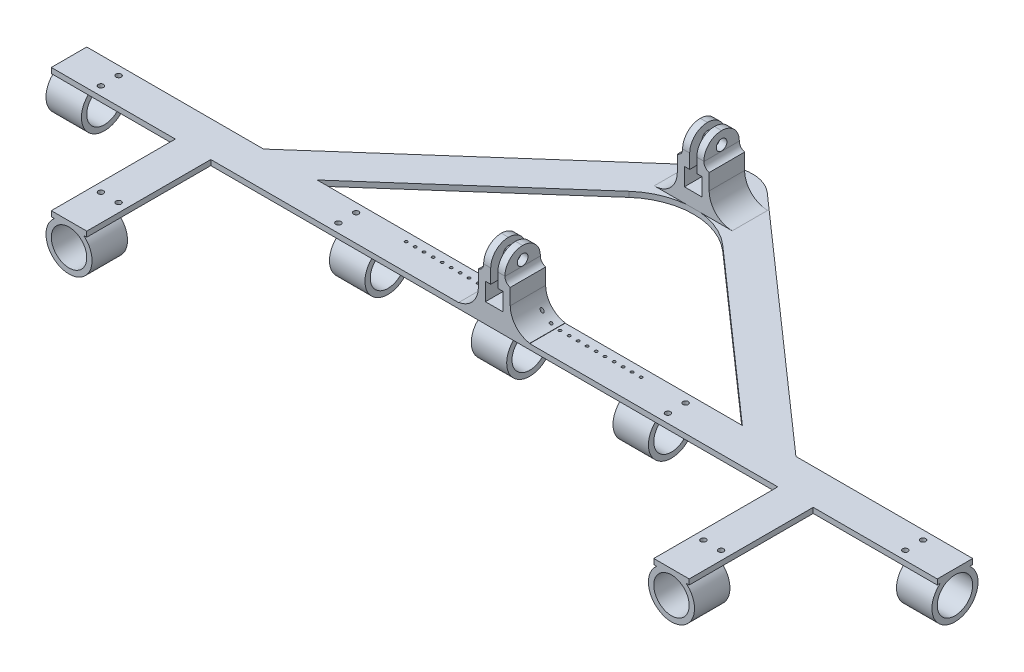
SolidWorks part; units mm, degrees
ref_plane "前视基准面" through (0, 0, 0) normal (0, 0, 1) x (1, 0, 0)
ref_plane "上视基准面" through (0, 0, 0) normal (0, 1, 0) x (1, 0, 0)
ref_plane "右视基准面" through (0, 0, 0) normal (1, 0, 0) x (0, 0, -1)
sketch "草图1" plane through (0, 0, 0) normal (0, 1, 0) x (1, 0, 0)
  line L1 (-125, 5) -> (125, 5)
  line L2 (-125, 5) -> (-125, -5)
  line L3 (-125, -5) -> (125, -5)
  line L4 (125, 5) -> (125, -5)
  line L5 (-125, 5) -> (125, -5) construction
  line L6 (-125, -5) -> (125, 5) construction
  point P0 (0, 0)
  dimension "D1" = 250
  dimension "D2" = 10
extrude "凸台-拉伸1" add sketch "草图1" along normal blind 1.5
sketch "草图4" plane through (0, 0, 0) normal (0, -1, 0) x (1, 0, 0)
  line L1 (-5, 7.1337) -> (5, 7.1337)
  line L2 (-5, 7.1337) -> (-5, -7.1337)
  line L3 (-5, -7.1337) -> (5, -7.1337)
  line L4 (5, 7.1337) -> (5, -7.1337)
  line L5 (-5, 7.1337) -> (5, -7.1337) construction
  line L6 (-5, -7.1337) -> (5, 7.1337) construction
  point P0 (0, 0)
  dimension "D1" = 10
  dimension "D2" = 14.2673
extrude "凸台-拉伸3" add sketch "草图4" along normal blind 11.5
sketch "草图5" plane through (5, 0, 0) normal (1, 0, 0) x (0, 0, -1)
  line L0 (0, 0) -> (0, -5)
  line L1 (5, 0) -> (-5, 0) construction
  line L2 (-5, 1.5) -> (5, 1.5) construction
  circle A0 centre (0, -5) radius 5
  circle A1 centre (0, -5) radius 6.5
  line M1 (7.1337, 0) -> (5, 0)
  line M2 (5, 0) -> (-5, 0)
  line M3 (-5, 0) -> (-7.1337, 0)
  line M4 (-7.1337, 0) -> (-7.1337, -11.5)
  line M5 (-7.1337, -11.5) -> (7.1337, -11.5)
  line M6 (7.1337, -11.5) -> (7.1337, 0)
  dimension "D1" = 10
extrude "切除-拉伸1" cut sketch "草图5" against normal through all contours A1 M2 M3 M4 M5 | A1 M5 M6 M1 M2 | A0 region at (5, -8.4355, 3.4355) region at (5, -0.1353, -4.5767) region at (5, -7.2539, 6.2408)
sketch "草图6" plane through (0, 0, 0) normal (0, -1, 0) x (1, 0, 0)
  line L0 (0, 0) -> (40, 0)
  line L1 (-125, 5) -> (125, 5) construction
  line L3 (35, 6.5) -> (45, 6.5)
  line L4 (35, 6.5) -> (35, -6.5)
  line L5 (35, -6.5) -> (45, -6.5)
  line L6 (45, 6.5) -> (45, -6.5)
  line L7 (35, 6.5) -> (45, -6.5) construction
  line L8 (35, -6.5) -> (45, 6.5) construction
  dimension "D1" = 40
  dimension "D2" = 10
  dimension "D3" = 13
extrude "凸台-拉伸4" add sketch "草图6" along normal blind 11.5 contours L3 L6 L5 L4
sketch "草图7" plane through (45, 0, 0) normal (1, 0, 0) x (0, 0, -1)
  line L0 (0, -5) -> (0, 0)
  line L1 (-5, 0) -> (5, 0) construction
  line L2 (-5, 1.5) -> (5, 1.5) construction
  circle A0 centre (0, -5) radius 5
  circle A1 centre (0, -5) radius 6.5
  line M1 (-5, 0) -> (-6.5, 0)
  line M2 (-6.5, 0) -> (-6.5, -11.5)
  line M3 (-6.5, -11.5) -> (6.5, -11.5)
  line M4 (6.5, -11.5) -> (6.5, 0)
  line M5 (6.5, 0) -> (5, 0)
  line M6 (5, 0) -> (-5, 0)
  dimension "D1" = 10
extrude "切除-拉伸2" cut sketch "草图7" against normal through all contours A1 M6 M1 M2 | A1 M2 M3 | A1 M3 M4 | A1 M4 M5 M6 | A0 region at (45, -8.4355, 3.4355) region at (45, -1.2004, -5.8248) region at (45, -1.2004, 5.8248) region at (45, -10.0481, -5.0481) region at (45, -10.0481, 5.0481)
sketch "草图8" plane through (0, 0, 0) normal (0, -1, 0) x (1, 0, 0)
  line L0 (0, 0) -> (120, 0)
  line L1 (-125, 5) -> (125, 5) construction
  line L3 (115, 6.5) -> (125, 6.5)
  line L4 (115, 6.5) -> (115, -6.5)
  line L5 (115, -6.5) -> (125, -6.5)
  line L6 (125, 6.5) -> (125, -6.5)
  line L7 (115, 6.5) -> (125, -6.5) construction
  line L8 (115, -6.5) -> (125, 6.5) construction
  dimension "D1" = 120
  dimension "D2" = 10
  dimension "D3" = 13
extrude "凸台-拉伸5" add sketch "草图8" along normal blind 11.5 contours L3 L6 L5 L4
sketch "草图9" plane through (125, 0, 0) normal (1, 0, 0) x (0, 0, -1)
  line L0 (0, -5) -> (0, 0)
  line L1 (-5, 1.5) -> (5, 1.5) construction
  line L2 (-5, 0) -> (5, 0)
  circle A0 centre (0, -5) radius 5
  circle A1 centre (0, -5) radius 6.5
  line M2 (-5, 0) -> (-6.5, 0)
  line M3 (-6.5, 0) -> (-6.5, -11.5)
  line M4 (-6.5, -11.5) -> (6.5, -11.5)
  line M5 (6.5, -11.5) -> (6.5, 0)
  line M6 (6.5, 0) -> (5, 0)
  dimension "D1" = 10
extrude "切除-拉伸3" cut sketch "草图9" against normal through all contours A1 L2 M2 M3 | A1 M3 M4 | A1 M4 M5 | A1 L2 M5 M6 | A0 region at (125, -1.2004, 5.8248) region at (125, -1.5645, -3.4355) region at (125, -1.2004, -5.8248) region at (125, -10.0481, 5.0481) region at (125, -10.0481, -5.0481)
sketch "草图13" plane through (0, 0, 0) normal (0, -1, 0) x (1, 0, 0)
  line L0 (0, 0) -> (-40, 0)
  line L1 (-125, 5) -> (125, 5) construction
  line L3 (-45, 6.5) -> (-35, 6.5)
  line L4 (-45, 6.5) -> (-45, -6.5)
  line L5 (-45, -6.5) -> (-35, -6.5)
  line L6 (-35, 6.5) -> (-35, -6.5)
  line L7 (-45, 6.5) -> (-35, -6.5) construction
  line L8 (-45, -6.5) -> (-35, 6.5) construction
  dimension "D1" = 40
  dimension "D2" = 10
  dimension "D3" = 13
extrude "凸台-拉伸6" add sketch "草图13" along normal blind 11.5 contours L3 L6 L5 L4
sketch "草图15" plane through (-45, 0, 0) normal (-1, 0, 0) x (0, 0, 1)
  line L0 (0, 0) -> (0, -5)
  line L1 (-5, 1.5) -> (5, 1.5) construction
  circle A0 centre (0, -5) radius 5
  circle A1 centre (0, -5) radius 6.5
  line M1 (6.5, 0) -> (5, 0)
  line M2 (5, 0) -> (-5, 0)
  line M3 (-5, 0) -> (-6.5, 0)
  line M4 (-6.5, 0) -> (-6.5, -11.5)
  line M5 (-6.5, -11.5) -> (6.5, -11.5)
  line M6 (6.5, -11.5) -> (6.5, 0)
  dimension "D1" = 10
extrude "切除-拉伸5" cut sketch "草图15" against normal through all contours A1 M2 M3 M4 | A1 M4 M5 | A1 M6 M1 M2 | A1 M5 M6 | A0 region at (-45, -8.4355, -3.4355) region at (-45, -1.2004, 5.8248) region at (-45, -1.2004, -5.8248) region at (-45, -10.0481, 5.0481) region at (-45, -10.0481, -5.0481)
sketch "草图16" plane through (0, 0, 0) normal (0, -1, 0) x (1, 0, 0)
  line L0 (0, 0) -> (-120, 0)
  line L1 (-125, 5) -> (125, 5) construction
  line L3 (-125, 6.5) -> (-115, 6.5)
  line L4 (-125, 6.5) -> (-125, -6.5)
  line L5 (-125, -6.5) -> (-115, -6.5)
  line L6 (-115, 6.5) -> (-115, -6.5)
  line L7 (-125, 6.5) -> (-115, -6.5) construction
  line L8 (-125, -6.5) -> (-115, 6.5) construction
  dimension "D1" = 120
  dimension "D2" = 10
  dimension "D3" = 13
extrude "凸台-拉伸7" add sketch "草图16" along normal blind 11.5 contours L3 L6 L5 L4
sketch "草图17" plane through (-125, 0, 0) normal (-1, 0, 0) x (0, 0, 1)
  line L0 (0, -5) -> (0, 0)
  line L1 (-5, 1.5) -> (5, 1.5) construction
  line L2 (-5, 0) -> (5, 0)
  circle A0 centre (0, -5) radius 5
  circle A1 centre (0, -5) radius 6.5
  line M2 (-5, 0) -> (-6.5, 0)
  line M3 (-6.5, 0) -> (-6.5, -11.5)
  line M4 (-6.5, -11.5) -> (6.5, -11.5)
  line M5 (6.5, -11.5) -> (6.5, 0)
  line M6 (6.5, 0) -> (5, 0)
  dimension "D1" = 10
extrude "切除-拉伸6" cut sketch "草图17" against normal through all contours A1 L2 M2 M3 | A1 M3 M4 | A1 M4 M5 | A1 L2 M5 M6 | A0 region at (-125, -1.2004, -5.8248) region at (-125, -1.5645, 3.4355) region at (-125, -1.2004, 5.8248) region at (-125, -10.0481, -5.0481) region at (-125, -10.0481, 5.0481)
sketch "草图18" plane through (0, 0, 0) normal (0, -1, 0) x (1, 0, 0)
  line L0 (-117.1464, 2.5) -> (-107.1464, 2.5)
  line L1 (-125, 5) -> (125, 5) construction
  line L2 (-140.924, 0) -> (135.605, 0) construction
  line L3 (0, 37.3305) -> (0, -40.1844) construction
  line L4 (-117.1464, -2.5) -> (-107.1464, -2.5)
  line L5 (117.1464, -2.5) -> (107.1464, -2.5)
  line L6 (117.1464, 2.5) -> (107.1464, 2.5)
  line L7 (-51.9294, 2.5) -> (-41.9294, 2.5)
  line L8 (-51.9294, -2.5) -> (-41.9294, -2.5)
  line L9 (51.9294, -2.5) -> (41.9294, -2.5)
  line L10 (51.9294, 2.5) -> (41.9294, 2.5)
  line L11 (-113.5, 7.6526) -> (-113.5, -7.9222)
  line L12 (-115, -6.5) -> (-115, 6.5) construction
  line L13 (-46.5, 7.6526) -> (-46.5, -7.9222)
  line L14 (-45, 6.5) -> (-45, -6.5) construction
  line L15 (46.5, 7.6526) -> (46.5, -7.9222)
  line L16 (113.5, 7.6526) -> (113.5, -7.9222)
  line L17 (-1.8696, 2.5) -> (-11.8696, 2.5)
  line L18 (-1.8696, -2.5) -> (-11.8696, -2.5)
  line L19 (-6.5, 7.6526) -> (-6.5, -7.9222)
  line L20 (-5, 6.5) -> (-5, -6.5) construction
  circle A0 centre (-113.5, 2.5) radius 0.75
  circle A1 centre (-113.5, -2.5) radius 0.75
  circle A2 centre (-46.5, 2.5) radius 0.75
  circle A3 centre (-46.5, -2.5) radius 0.75
  circle A4 centre (46.5, -2.5) radius 0.75
  circle A5 centre (46.5, 2.5) radius 0.75
  circle A6 centre (113.5, -2.5) radius 0.75
  circle A7 centre (113.5, 2.5) radius 0.75
  circle A8 centre (-6.5, 2.5) radius 0.75
  circle A9 centre (-6.5, -2.5) radius 0.75
  point P44 (-113.5, 2.5)
  point P45 (-113.5, -2.5)
  point P50 (-46.5, 2.5)
  point P51 (-46.5, -2.5)
  point P64 (-6.5, 2.5)
  point P65 (-6.5, -2.5)
  dimension "D8" = 1.5
  dimension "D9" = 1.5
  dimension "D10" = 1.5
  dimension "D1" = 2.5
  dimension "D2" = 10
  dimension "D3" = 10
  dimension "D4" = 1.5
  dimension "D5" = 1.5
  dimension "D6" = 10
  dimension "D7" = 1.5
extrude "切除-拉伸8" cut sketch "草图18" against normal through all contours L11 A0 L0 | L0 A0 L11 | L11 A0 L0 | L0 A0 L11 | A1 L4 L11 | A1 L11 L4 | A1 L4 L11 | A1 L11 L4 | L13 A2 L7 | L7 A2 L13 | L7 A2 L13 | L13 A2 L7 | A3 L8 L13 | A3 L13 L8 | A3 L13 L8 | A3 L8 L13 | L17 A8 L19 | L19 A8 L17 | L19 A8 L17 | L17 A8 L19 | A9 L18 L19 | A9 L19 L18 | A9 L18 L19 | A9 L19 L18 | A5 L10 L15 | A5 L15 L10 | A5 L10 L15 | A5 L15 L10 | L15 A4 L9 | L9 A4 L15 | L15 A4 L9 | L9 A4 L15 | A7 L6 L16 | A7 L16 L6 | A7 L6 L16 | A7 L16 L6 | L16 A6 L5 | L5 A6 L16 | L16 A6 L5 | L5 A6 L16 region at (-113.8183, 0, 2.8183) region at (-113.1817, 0, -2.1817) region at (-113.8183, 0, -2.1817) region at (-113.8183, 0, 2.1817) region at (-113.1817, 0, 2.8183) region at (-113.1817, 0, 2.1817) region at (-113.8183, 0, -2.8183) region at (-113.1817, 0, -2.8183) region at (113.8183, 0, -2.8183) region at (113.8183, 0, -2.1817) region at (113.1817, 0, 2.1817) region at (113.8183, 0, 2.1817) region at (113.1817, 0, -2.8183) region at (113.1817, 0, -2.1817) region at (113.8183, 0, 2.8183) region at (113.1817, 0, 2.8183) region at (-46.8183, 0, 2.8183) region at (-46.1817, 0, -2.1817) region at (-46.8183, 0, -2.1817) region at (-46.8183, 0, 2.1817) region at (-46.1817, 0, 2.8183) region at (-46.1817, 0, 2.1817) region at (-46.8183, 0, -2.8183) region at (-46.1817, 0, -2.8183) region at (46.8183, 0, -2.8183) region at (46.8183, 0, -2.1817) region at (46.1817, 0, 2.1817) region at (46.8183, 0, 2.1817) region at (46.1817, 0, -2.8183) region at (46.1817, 0, -2.1817) region at (46.8183, 0, 2.8183) region at (46.1817, 0, 2.8183) region at (-6.1817, 0, 2.1817) region at (-6.1817, 0, 2.8183) region at (-6.1817, 0, -2.1817) region at (-6.8183, 0, -2.1817) region at (-6.8183, 0, 2.1817) region at (-6.8183, 0, 2.8183) region at (-6.8183, 0, -2.8183) region at (-6.1817, 0, -2.8183)
sketch "草图22" plane through (0, 0, 0) normal (0, -1, 0) x (1, 0, 0)
  line L0 (0, 107.0541) -> (0, -222.8841) construction
  line L1 (0, 0) -> (-60, 0)
  line L2 (-125, 5) -> (125, 5) construction
  line L4 (125, -5) -> (-125, -5) construction
  line L5 (60, 0) -> (60, -5)
  line L6 (-60, -5) -> (0, -57.915)
  line L7 (0, -57.915) -> (60, -5)
  line L8 (-75.1186, -5) -> (0, -71.2484)
  line L9 (0, -71.2484) -> (75.1186, -5)
  line L10 (-60, -5) -> (-75.1186, -5)
  line L11 (60, -5) -> (75.1186, -5)
  line M16 (-125, -5) -> (125, -5)
  dimension "D1" = 60
  dimension "D2" = 80
  dimension "D3" = 10
extrude "凸台-拉伸10" add sketch "草图22" against normal blind 1.5 separate body contours L0 L6 L8 M16 | L7 L0 L9 M16 region at (33.9206, 0, -34.9152) region at (-33.9206, 0, -34.9152)
fillet "圆角1" radius 10 1 edges at (0, 0.75, -71.2484)
fillet "圆角2" radius 20 1 edges at (0, 0.75, -57.915)
sketch "草图24" plane through (0, 1.5, 0) normal (0, 1, 0) x (1, 0, 0)
  line L1 (-10, 5) -> (10, 5)
  line L2 (-10, 5) -> (-10, -5)
  line L3 (-10, -5) -> (10, -5)
  line L4 (10, 5) -> (10, -5)
  line L5 (-10, 5) -> (10, -5) construction
  line L6 (-10, -5) -> (10, 5) construction
  point P0 (0, 0)
  dimension "D1" = 20
  dimension "D2" = 10
extrude "凸台-拉伸11" add sketch "草图24" along normal blind 20
sketch "草图25" plane through (0, 0, 5) normal (0, 0, 1) x (1, 0, 0)
  line L1 (0, 23.6125) -> (0, -2.2867) construction
sketch "草图26" plane through (0, 1.5, 0) normal (0, 1, 0) x (1, 0, 0)
  line L0 (0, 141.3842) -> (0, -41.294) construction
  line L2 (-11, 61.1419) -> (11, 61.1419)
  line L3 (-11, 61.1419) -> (-11, 51.1419)
  line L4 (-11, 51.1419) -> (11, 51.1419)
  line L5 (11, 61.1419) -> (11, 51.1419)
  line L6 (-11, 61.1419) -> (11, 51.1419) construction
  line L7 (-11, 51.1419) -> (11, 61.1419) construction
  point P6 (0, 56.1419)
  dimension "D1" = 22
  dimension "D2" = 10
extrude "凸台-拉伸12" add sketch "草图26" along normal blind 20
sketch "草图41" plane through (0, 0, 5) normal (0, 0, 1) x (1, 0, 0)
  line L0 (125, 0.75) -> (-129.8236, 0.75) construction
  line L1 (125, 1.5) -> (125, 0) construction
  line L2 (125, 0.75) -> (85, 0.75)
  line L4 (80, 1.5) -> (90, 1.5)
  line L5 (80, 1.5) -> (80, 0)
  line L6 (80, 0) -> (90, 0)
  line L7 (90, 1.5) -> (90, 0)
  line L8 (80, 1.5) -> (90, 0) construction
  line L9 (80, 0) -> (90, 1.5) construction
  line M8 (-125, 0) -> (125, 0)
  line M10 (125, 1.5) -> (10, 1.5)
  dimension "D1" = 40
  dimension "D2" = 10
  dimension "D3" = 1.5
extrude "凸台-拉伸13" add sketch "草图41" along normal blind 35 contours L7 L5 M10 M8 region at (85, 1.3989, 5)
sketch "草图42" plane through (0, 0, 5) normal (0, 0, 1) x (1, 0, 0)
  line L0 (-125, 0.75) -> (-85, 0.75)
  line L1 (-125, 1.5) -> (-125, 0) construction
  line L3 (-90, 1.5) -> (-80, 1.5)
  line L4 (-90, 1.5) -> (-90, 0)
  line L5 (-90, 0) -> (-80, 0)
  line L6 (-80, 1.5) -> (-80, 0)
  line L7 (-90, 1.5) -> (-80, 0) construction
  line L8 (-90, 0) -> (-80, 1.5) construction
  line M14 (-10, 1.5) -> (-125, 1.5)
  line M16 (-125, 0) -> (80, 0)
  dimension "D1" = 40
  dimension "D2" = 10
  dimension "D3" = 1.5
extrude "凸台-拉伸14" add sketch "草图42" along normal blind 35 contours L6 L4 M14 M16 region at (-85, 1.3989, 5)
sketch "草图43" plane through (0, 0, 40) normal (0, 0, 1) x (1, 0, 0)
  line L0 (85, 0) -> (85, 3.5011) construction
  line L1 (80, 0) -> (90, 0) construction
  line L2 (85, -5) -> (85, 0)
  line L3 (90, 1.5) -> (80, 1.5) construction
  circle A0 centre (85, -5) radius 5
  circle A1 centre (85, -5) radius 6.5
  line M4 (80, 0) -> (90, 0)
  dimension "D1" = 10
extrude "凸台-拉伸21" add sketch "草图43" against normal blind 10 contours A1 A0 M4 | L0 A1 M4 | L0 A1 M4 region at (87.0767, -0.1736, 40) region at (85, 0.6064, 40)
sketch "草图44" plane through (0, 0, 40) normal (0, 0, 1) x (1, 0, 0)
  line L0 (-85, 0) -> (-85, 2.8539) construction
  line L1 (-90, 0) -> (-80, 0) construction
  line L2 (-85, 0) -> (-85, -4.9374) construction
  line L3 (-85, -5) -> (-85, 0)
  line L4 (-80, 1.5) -> (-90, 1.5) construction
  circle A0 centre (-85, -5) radius 5
  circle A1 centre (-85, -5) radius 6.5
  line M4 (-90, 0) -> (-80, 0)
  dimension "D1" = 10
extrude "凸台-拉伸22" add sketch "草图44" against normal blind 10 contours A1 A0 M4 | A1 M4 region at (-82.9233, -0.1736, 40) region at (-85, 0.6064, 40)
sketch "草图45" plane through (0, 0, 0) normal (0, -1, 0) x (1, 0, 0)
  line L0 (-87.5, 32.9839) -> (-87.5, 15.0757)
  line L1 (-90, 40) -> (-90, 5) construction
  line L2 (-85, 27.5552) -> (-85, 13.5975) construction
  line L3 (-82.5, 32.9839) -> (-82.5, 15.0757)
  line L4 (-93.2419, 28.5) -> (-76.3973, 28.5)
  line L5 (-91.5, 30) -> (-78.5, 30) construction
  line L7 (0, 29.7177) -> (0, -25.9175) construction
  circle A1 centre (-87.5, 28.5) radius 0.75
  circle A2 centre (-82.5, 28.5) radius 0.75
  circle A3 centre (82.5, 28.5) radius 0.75
  circle A4 centre (87.5, 28.5) radius 0.75
  point P12 (-87.5, 28.5)
  point P13 (-82.5, 28.5)
  dimension "D3" = 1.5
  dimension "D4" = 1.5
  dimension "D1" = 2.5
  dimension "D2" = 1.5
extrude "切除-拉伸37" cut sketch "草图45" against normal through all contours L0 A1 L4 | L4 A1 L0 | L0 A1 L4 | L4 A1 L0 | L4 A2 L3 | L3 A2 L4 | L4 A2 L3 | L3 A2 L4 | A3 | A4 region at (-87.1817, 0, 28.8183) region at (-82.8183, 0, 28.8183) region at (-82.8183, 0, 28.1817) region at (-87.8183, 0, 28.8183) region at (-87.1817, 0, 28.1817) region at (-87.8183, 0, 28.1817) region at (-82.1817, 0, 28.1817) region at (-82.1817, 0, 28.8183) region at (82.5, 0, 28.5) region at (87.5, 0, 28.5)
sketch "草图52" plane through (0, 0, 0) normal (0, -1, 0) x (1, 0, 0)
  line L0 (-6.5, -2.5) -> (-36.7093, -2.5) construction
  line L1 (5, -6.5) -> (5, 6.5) construction
  line L2 (-6.5, -2.5) -> (46.5, -2.5) construction
  line L3 (60, -5) -> (-60, -5) construction
  line L4 (0, -7.8299) -> (0, 11.6193) construction
  circle A0 centre (-9.5, -2.5) radius 0.4
  circle A1 centre (-12.04, -2.5) radius 0.4
  circle A2 centre (-14.58, -2.5) radius 0.4
  circle A3 centre (-17.12, -2.5) radius 0.4
  circle A4 centre (-19.66, -2.5) radius 0.4
  circle A5 centre (-22.2, -2.5) radius 0.4
  circle A6 centre (-24.74, -2.5) radius 0.4
  circle A7 centre (-27.28, -2.5) radius 0.4
  circle A8 centre (-29.82, -2.5) radius 0.4
  circle A9 centre (-32.36, -2.5) radius 0.4
  circle A10 centre (6, -2.5) radius 0.4
  circle A11 centre (8.54, -2.5) radius 0.4
  circle A12 centre (11.08, -2.5) radius 0.4
  circle A13 centre (13.62, -2.5) radius 0.4
  circle A14 centre (16.16, -2.5) radius 0.4
  circle A15 centre (18.7, -2.5) radius 0.4
  circle A16 centre (21.24, -2.5) radius 0.4
  circle A17 centre (23.78, -2.5) radius 0.4
  circle A18 centre (26.32, -2.5) radius 0.4
  circle A19 centre (28.86, -2.5) radius 0.4
  circle A20 centre (31.4, -2.5) radius 0.4
  circle A21 centre (33.94, -2.5) radius 0.4
  dimension "D1" = 3
  dimension "D9" = 2.54
  dimension "D12" = 2.54
  dimension "D2" = 2.54
  dimension "D3" = 2.54
  dimension "D4" = 2.54
  dimension "D5" = 2.54
  dimension "D6" = 2.54
  dimension "D7" = 2.54
  dimension "D8" = 2.54
  dimension "D10" = 0.8
  dimension "D13" = 1
  dimension "D14" = 2.54
  dimension "D15" = 2.54
  dimension "D16" = 2.54
  dimension "D17" = 2.54
  dimension "D18" = 2.54
  dimension "D19" = 2.54
  dimension "D20" = 2.54
  dimension "D21" = 2.54
  dimension "D22" = 2.54
  dimension "D23" = 2.54
  dimension "D11" = 2.54
extrude "切除-拉伸47" cut sketch "草图52" against normal through all
sketch "草图53" plane through (0, 0, 5) normal (0, 0, 1) x (1, 0, 0)
  line L0 (0, 23.6125) -> (0, -2.2867) construction
  line L1 (0, 23.6125) -> (0, -2.2867) construction
  line L2 (-2.5, 10.5) -> (2.5, 10.5)
  line L3 (-2.5, 10.5) -> (-2.5, 5.5)
  line L4 (-2.5, 5.5) -> (2.5, 5.5)
  line L5 (2.5, 10.5) -> (2.5, 5.5)
  line L6 (-2.5, 10.5) -> (2.5, 5.5) construction
  line L7 (-2.5, 5.5) -> (2.5, 10.5) construction
  line L8 (-80, 0) -> (80, 0) construction
  line L9 (-4.5, 12.5) -> (-4.5, 8)
  line L10 (-11, 1.5) -> (-5.2878, 1.5)
  line L11 (-11, 1.5) -> (-2.0613, 1.5) construction
  line L12 (-4.5, 12.5) -> (4.5, 12.5)
  line L13 (-1, 12.5) -> (-1, 19.5)
  line L14 (-1, 19.5) -> (-3, 19.5)
  line L15 (-3, 19.5) -> (-3, 12.5)
  line L16 (1, 12.5) -> (1, 19.5)
  line L17 (1, 19.5) -> (3, 19.5)
  line L18 (3, 19.5) -> (3, 12.5)
  line L19 (4.5, 12.5) -> (4.5, 8)
  line L20 (-1, 12.5) -> (-1, 10.5)
  line L21 (1, 12.5) -> (1, 10.5)
  line L22 (-10, 21.5) -> (-11, 21.5)
  line L23 (-11, 21.5) -> (-11, 1.5)
  line L24 (-11, 1.5) -> (-10, 1.5)
  line L25 (-10, 1.5) -> (-10, 21.5)
  line L26 (11, 21.5) -> (10, 21.5)
  line L27 (10, 21.5) -> (10, 1.5)
  line L28 (10, 1.5) -> (11, 1.5)
  line L29 (11, 21.5) -> (11, 1.5)
  arc A0 (-11, 1.5) -> (-4.5, 8) centre (-11, 8) ccw
  arc A1 (11, 1.5) -> (4.5, 8) centre (11, 8) cw
  point P0 (0, 8)
  point P31 (0, 12.5)
  line M7 (10, 21.5) -> (-10, 21.5)
  line M8 (-10, 21.5) -> (-10, 1.5)
  dimension "D1" = 8
  dimension "D5" = 2
  dimension "D2" = 5
  dimension "D3" = 5
  dimension "D4" = 2
  dimension "D6" = 7
  dimension "D7" = 1
  dimension "D8" = 2
extrude "切除-拉伸49" cut sketch "草图53" against normal through all contours A1 L27 A0 L9 L12 L15 L14 L13 L16 L17 L18 L19 M7 M8 | L5 L2 L3 L4 | L21 L12 L20 L2 | L23 A0 L22 M8 | A1 L29 L26 L27 region at (0, 8, 5) region at (0, 11.5, 5) region at (0, 13.3594, 5) region at (-10.5003, 11.5129, 5) region at (10.5003, 11.5129, 5)
fillet "圆角3" radius 5 8 edges at (2, 19.5, -61.1419) (-2, 19.5, -51.1419) (-2, 19.5, -61.1419) (2, 19.5, -51.1419) (-2, 19.5, 5) (-2, 19.5, -5) (2, 19.5, -5) (2, 19.5, 5)
sketch "草图55" plane through (3, 0, 0) normal (1, 0, 0) x (0, 0, -1)
  line L0 (0, 19.5) -> (0, 16)
  circle A0 centre (0, 16) radius 1.5
  dimension "D1" = 3.5
  dimension "D2" = 3
extrude "切除-拉伸50" cut sketch "草图55" against normal through all and the other way through all contours A0 region at (3, 14.9693, 1.0307)
sketch "草图56" plane through (3, 0, 0) normal (1, 0, 0) x (0, 0, -1)
  line L0 (56.1419, 19.5) -> (56.1419, 16)
  circle A0 centre (56.1419, 16) radius 1.5
  dimension "D2" = 3
  dimension "D1" = 3.5
extrude "切除-拉伸51" cut sketch "草图56" against normal through all contours A0 region at (3, 14.9693, -55.1112)
fillet "圆角4" radius 2 4 edges at (-3, 12.5, -56.1419) (3, 12.5, -56.1419) (-3, 12.5, 0) (3, 12.5, 0)
